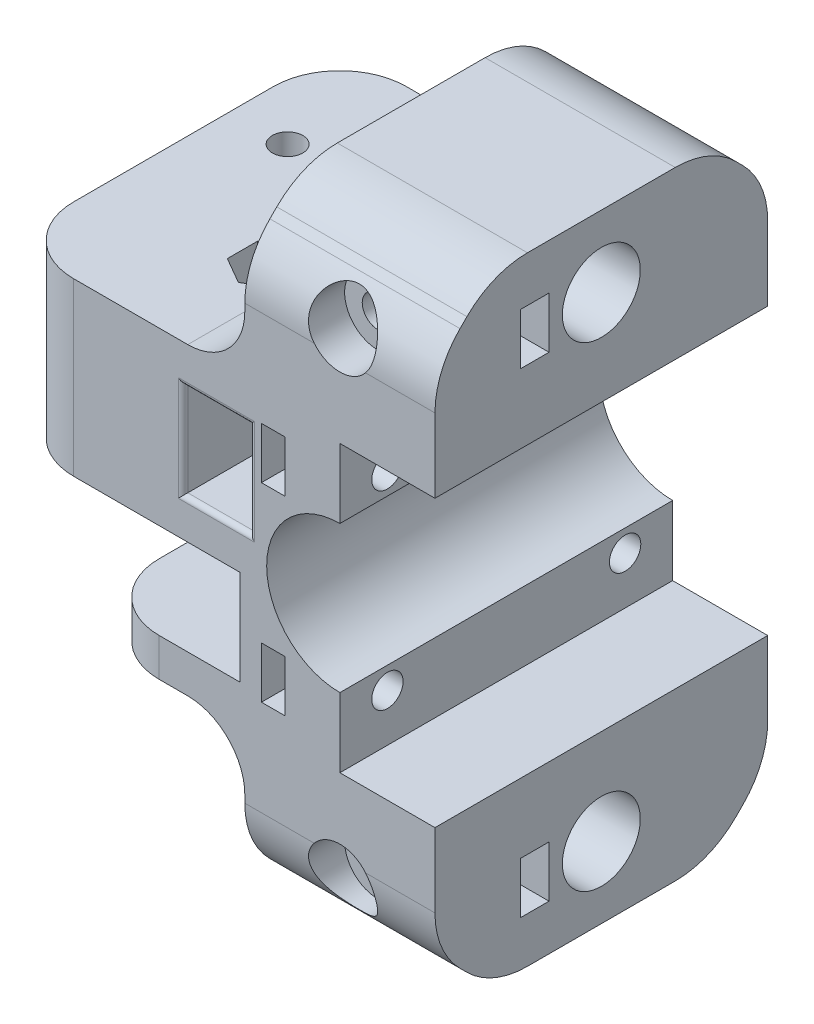
SolidWorks part; units mm, degrees
ref_plane "Plano frontal" through (0, 0, 0) normal (0, 0, 1) x (1, 0, 0)
ref_plane "Plano superior" through (0, 0, 0) normal (0, 1, 0) x (1, 0, 0)
ref_plane "Plano direito" through (0, 0, 0) normal (1, 0, 0) x (0, 0, -1)
sketch "Esboço2" plane through (0, 0, 0) normal (0, 0, 1) x (1, 0, 0)
  line L0 (-10, 16) -> (-10, 32.5)
  line L1 (-10, -32.5) -> (10, -32.5)
  line L2 (-10, -32.5) -> (-10, -16)
  line L3 (-10, 32.5) -> (10, 32.5)
  line L4 (10, -32.5) -> (10, 32.5)
  line L5 (-10, -32.5) -> (10, 32.5) construction
  line L6 (-10, 32.5) -> (10, -32.5) construction
  line L7 (-35, 16) -> (-10, 16)
  line L8 (-35, 16) -> (-35, 12)
  line L9 (-26, -16) -> (-10, -16)
  line L10 (0, 0) -> (-50.7474, 0) construction
  line L11 (-35, 16) -> (-10, -16) construction
  line L12 (-35, -16) -> (-10, 16) construction
  line L13 (-16.5, 2) -> (-9.5, 2)
  line L14 (-16.5, 2) -> (-16.5, 12)
  line L15 (-16.5, 12) -> (-9.5, 12)
  line L16 (-9.5, 2) -> (-9.5, 12)
  line L17 (-16.5, 2) -> (-9.5, 12) construction
  line L18 (-16.5, 12) -> (-9.5, 2) construction
  line L19 (-18.5, 12) -> (-35, 12)
  line L20 (-18.5, 12) -> (-18.5, 2)
  line L21 (-18.5, 2) -> (-35, 2)
  line L22 (-35, -2) -> (-26, -2)
  line L23 (-18.5, 12) -> (-35, 2) construction
  line L24 (-18.5, 2) -> (-35, 12) construction
  line L25 (-9.5, -2) -> (-26, -2)
  line L26 (-9.5, -2) -> (-9.5, -12)
  line L27 (-9.5, -12) -> (-26, -12)
  line L29 (-26, -12) -> (-26, -16)
  line L31 (-35, 2) -> (-35, -2)
  line L33 (-9.5, -2) -> (-26, -12) construction
  line L34 (-9.5, -12) -> (-26, -2) construction
  circle A0 centre (0, 0) radius 7.7
  point P7 (-22.5, 0)
  point P12 (-13, 7)
  point P18 (-26.75, 7)
  point P26 (-17.75, -7)
  dimension "D1" = 15.4
  dimension "D2" = 65
  dimension "D3" = 20
  dimension "D4" = 32
  dimension "D5" = 25
  dimension "D6" = 4
  dimension "D7" = 7
  dimension "D8" = 2
  dimension "D10" = 0.5
  dimension "D11" = 10
  dimension "D12" = 4
extrude "Ressalto-extrusão1" add sketch "Esboço2" along normal blind 35
sketch "Esboço3" plane through (-10, 0, 0) normal (-1, 0, 0) x (0, 0, 1)
  line L0 (0, 0) -> (35, 0) construction
  line L2 (35, 26.5) -> (29, 32.5)
  line L3 (35, 32.5) -> (35, 16) construction
  line L4 (17.5, 32.5) -> (17.5, 16) construction
  line L5 (23, 22.3) -> (23, 27.7)
  line L6 (23, 22.3) -> (26, 22.3)
  line L7 (26, 22.3) -> (26, 27.7)
  line L8 (23, 27.7) -> (26, 27.7)
  line L9 (23, 22.3) -> (26, 27.7) construction
  line L10 (26, 22.3) -> (23, 27.7) construction
  line L20 (26, -22.3) -> (23, -27.7) construction
  line L21 (23, -22.3) -> (26, -27.7) construction
  line L25 (23, -27.7) -> (26, -27.7)
  line L26 (26, -22.3) -> (26, -27.7)
  line L27 (23, -22.3) -> (26, -22.3)
  line L28 (23, -22.3) -> (23, -27.7)
  line L29 (35, 32.5) -> (0, 32.5) construction
  line L30 (35, 16) -> (0, 16) construction
  line L31 (0, 26.5) -> (6, 32.5)
  line L32 (0, 26.5) -> (0, 32.5)
  line L33 (0, 32.5) -> (6, 32.5)
  line L34 (35, 26.5) -> (35, 32.5)
  line L35 (35, 32.5) -> (29, 32.5)
  line L36 (35, -32.5) -> (29, -32.5)
  line L37 (35, -26.5) -> (35, -32.5)
  line L38 (0, -32.5) -> (6, -32.5)
  line L39 (0, -26.5) -> (0, -32.5)
  line L40 (0, -26.5) -> (6, -32.5)
  line L41 (35, -26.5) -> (29, -32.5)
  circle A0 centre (17.5, 25) radius 4.1
  circle A1 centre (17.5, -25) radius 4.1
  circle A4 centre (30, 10) radius 1.65
  circle A5 centre (5, 10) radius 1.65
  circle A6 centre (5, -10) radius 1.65
  circle A7 centre (30, -10) radius 1.65
  point P11 (24.5, 25)
  point P33 (24.5, -25)
  point P37 (17.5, 32.5)
  line M2 (0, 32.5) -> (0, 16)
  line M4 (35, 16) -> (35, 32.5)
  line M5 (35, 32.5) -> (0, 32.5)
  dimension "D1" = 4.1
  dimension "D13" = 3.3
  dimension "D14" = 25
  dimension "D15" = 20
  dimension "D2" = 50
  dimension "D3" = 5.4
  dimension "D4" = 3
  dimension "D5" = 7
  dimension "D6" = 6
extrude "Corte-extrusão1" cut sketch "Esboço3" against normal through all contours L31 M2 M5 | A0 M4 | L2 M4 M5 | A5 | A4 | A6 | A7 | A1 | L40 L39 L38 | L37 L41 L36 region at (-10, 30.5, 2) region at (-10, 30.5, 33) region at (-10, -30.5, 33) region at (-10, -30.5, 2) region at (-10, 25, 17.5) region at (-10, -25, 17.5) region at (-10, 10, 30) region at (-10, 10, 5) region at (-10, -10, 5) region at (-10, -10, 30)
extrude "Corte-extrusão11" cut sketch "Esboço3<3>" along normal through all from surface contours L27 L28 L25 L26 | L6 L7 L8 L5 region at (-10, -25, 24.5) starting at face at (10, 10, 6.65)
sketch "Esboço3<3>" plane through (-10, 0, 0) normal (-1, 0, 0) x (0, 0, 1) same geometry as "Esboço3"
sketch "Esboço4" plane through (0, 16, 0) normal (0, 1, 0) x (1, 0, 0)
  line L1 (10, -17.5) -> (-35, -17.5) construction
  line L2 (10, -29) -> (10, -6) construction
  line L5 (-35, -35) -> (-35, 0) construction
  line L6 (-29, -11.5) -> (-29, -17.5) construction
  line L8 (-19, -23.5) -> (-19, -17.5) construction
  circle A0 centre (-29, -11.5) radius 1.6
  circle A1 centre (-29, -11.5) radius 5 construction
  circle A2 centre (-29, -11.5) radius 7 construction
  circle A3 centre (-19, -23.5) radius 1.6
  circle A4 centre (-19, -23.5) radius 5 construction
  dimension "D2" = 14
  dimension "D3" = 2
  dimension "D1" = 3.2
  dimension "D5" = 10
  dimension "D4" = 29
  dimension "D6" = 19
extrude "Corte-extrusão2" cut sketch "Esboço4" against normal through all both and the other way through all contours A0 region at (-29, 16, 11.5)
fillet "Filete2" radius 7 6 edges at (-35, 14, 35) (-35, 0, 35) (-35, 0, 0) (-35, 14, 0) (-26, -14, 35) (-26, -14, 0)
sketch "Esboço8" plane through (10, 0, 0) normal (1, 0, 0) x (0, 0, -1)
  line L1 (-35, 15) -> (0, 15)
  line L2 (-35, 15) -> (-35, -15)
  line L3 (-35, -15) -> (0, -15)
  line L4 (0, 15) -> (0, -15)
  line L6 (-35, -26.5) -> (-35, 26.5) construction
  line L7 (0, -26.5) -> (0, 26.5) construction
  point P5 (0, 0)
  dimension "D1" = 30
extrude "Corte-extrusão4" cut sketch "Esboço8" against normal blind 10
sketch "Esboço9" plane through (0, 0, 0) normal (0, 0, -1) x (-1, 0, 0)
  line L0 (0, 0) -> (46.8787, 0) construction
  line L1 (5.75, 12.7) -> (8.25, 12.7)
  line L2 (5.75, 12.7) -> (5.75, 7.3)
  line L3 (5.75, 7.3) -> (8.25, 7.3)
  line L4 (8.25, 12.7) -> (8.25, 7.3)
  line L5 (5.75, 12.7) -> (8.25, 7.3) construction
  line L6 (5.75, 7.3) -> (8.25, 12.7) construction
  line L7 (0, 7.7) -> (0, 15) construction
  line L8 (5.75, -7.3) -> (8.25, -12.7) construction
  line L9 (5.75, -12.7) -> (8.25, -7.3) construction
  line L10 (8.25, -12.7) -> (8.25, -7.3)
  line L11 (5.75, -7.3) -> (8.25, -7.3)
  line L12 (5.75, -12.7) -> (5.75, -7.3)
  line L13 (5.75, -12.7) -> (8.25, -12.7)
  point P0 (7, 10)
  point P14 (7, -10)
  dimension "D1" = 20
  dimension "D2" = 5.4
  dimension "D3" = 2.5
  dimension "D4" = 7
extrude "Corte-extrusão5" cut sketch "Esboço9" against normal through all
extrude "Corte-extrusão6" cut sketch "Esboço4<3>" against normal through all contours A3 region at (-19, 16, 23.5)
sketch "Esboço4<3>" plane through (0, 16, 0) normal (0, 1, 0) x (1, 0, 0) same geometry as "Esboço4"
sketch "Esboço12" plane through (0, -12, 0) normal (0, 1, 0) x (1, 0, 0)
  line L0 (-10.5, -23.5) -> (-10.5, -35)
  line L2 (-10.5, -35) -> (-9.5, -35)
  line L3 (-9.5, -35) -> (-9.5, 0)
  line L5 (-26, -28) -> (-26, -7) construction
  line L6 (-26, -28) -> (-26, -7) construction
  line L7 (-26, -7) -> (-26, -15)
  line L8 (-26, -15) -> (-19, -15)
  line L9 (10, 0) -> (-10, 0) construction
  line L11 (-9.5, 0) -> (-19, 0)
  line L13 (-9.5, -35) -> (-9.5, 0) construction
  line L14 (-10, -35) -> (-28, -35) construction
  arc A0 (-10.5, -23.5) -> (-19, -15) centre (-19, -23.5) ccw
  arc A1 (-19, 0) -> (-26, -7) centre (-19, -7) ccw
  dimension "D1" = 17
extrude "Ressalto-extrusão2" add sketch "Esboço12" along normal blind 10
sketch "Esboço13" plane through (0, -2, 0) normal (0, -1, 0) x (1, 0, 0)
  line L1 (-29, 14.6754) -> (-31.75, 13.0877)
  line L2 (-31.75, 13.0877) -> (-31.75, 9.9123)
  line L3 (-31.75, 9.9123) -> (-29, 8.3246)
  line L4 (-29, 8.3246) -> (-26.25, 9.9123)
  line L5 (-26.25, 9.9123) -> (-26.25, 13.0877)
  line L6 (-26.25, 13.0877) -> (-29, 14.6754)
  circle A0 centre (-29, 11.5) radius 2.75 construction
  dimension "D1" = 5.5
extrude "Corte-extrusão9" cut sketch "Esboço13" against normal blind 2
sketch "Esboço14" plane through (0, 2, 0) normal (0, 1, 0) x (1, 0, 0)
  line L0 (-20.5, -11.5) -> (-20.5, 0)
  line L1 (-18.5, 0) -> (-28, 0) construction
  line L2 (-20.5, 0) -> (-18.5, 0)
  line L3 (-18.5, 0) -> (-18.5, -35)
  line L5 (-35, -28) -> (-35, -7) construction
  line L6 (-35, -28) -> (-35, -20)
  line L7 (-35, -20) -> (-29, -20)
  line L10 (-28, -35) -> (-18.5, -35)
  arc A0 (-29, -20) -> (-20.5, -11.5) centre (-29, -11.5) ccw
  arc A1 (-35, -28) -> (-28, -35) centre (-28, -28) ccw
  dimension "D1" = 17
extrude "Ressalto-extrusão3" add sketch "Esboço14" along normal blind 10
sketch "Esboço15" plane through (0, 16, 0) normal (0, 1, 0) x (1, 0, 0)
  line L1 (-19, -26.6754) -> (-16.25, -25.0877)
  line L2 (-16.25, -25.0877) -> (-16.25, -21.9123)
  line L3 (-16.25, -21.9123) -> (-19, -20.3246)
  line L4 (-19, -20.3246) -> (-21.75, -21.9123)
  line L5 (-21.75, -21.9123) -> (-21.75, -25.0877)
  line L6 (-21.75, -25.0877) -> (-19, -26.6754)
  circle A0 centre (-19, -23.5) radius 2.75 construction
  dimension "D1" = 5.5
extrude "Corte-extrusão10" cut sketch "Esboço15" against normal blind 14
fillet "Filete3" radius 0.5 8 edges at (-16.5, 7, 0) (-9.5, 7, 0) (-9.5, 7, 35) (-16.5, 7, 35) (-13, 2, 35) (-13, 12, 35) (-13, 12, 0) (-13, 2, 0)
fillet "Filete4" radius 9 8 edges at (0, -26.5, 35) (0, -32.5, 29) (0, -26.5, 0) (0, -32.5, 6) (0, 26.5, 35) (0, 32.5, 29) (0, 32.5, 6) (0, 26.5, 0)
fillet "Filete5" radius 6 2 edges at (-10, -16, 17.5) (-10, 16, 17.5)
sketch "Esboço17" plane through (0, 0, 23) normal (0, 0, 1) x (1, 0, 0)
  line L0 (-10, 22.3) -> (-10, 27.7) construction
  line L1 (0, 0) -> (12.2144, 0) construction
  circle A0 centre (0, 25) radius 1.65
  circle A1 centre (0, -25) radius 1.65
  point P4 (-10, 25)
  dimension "D1" = 3.3
extrude "Corte-extrusão12" cut sketch "Esboço17" against normal blind 5 and the other way through all
sketch "Esboço18" plane through (0, 0, 23) normal (0, 0, 1) x (1, 0, 0)
  circle A0 centre (0, 25) radius 3.5
  circle A1 centre (0, -25) radius 3.5
  dimension "D1" = 7
extrude "Corte-extrusão14" cut sketch "Esboço18" against normal blind 4 from vertex starting at point (10, 22.7721, 35)
